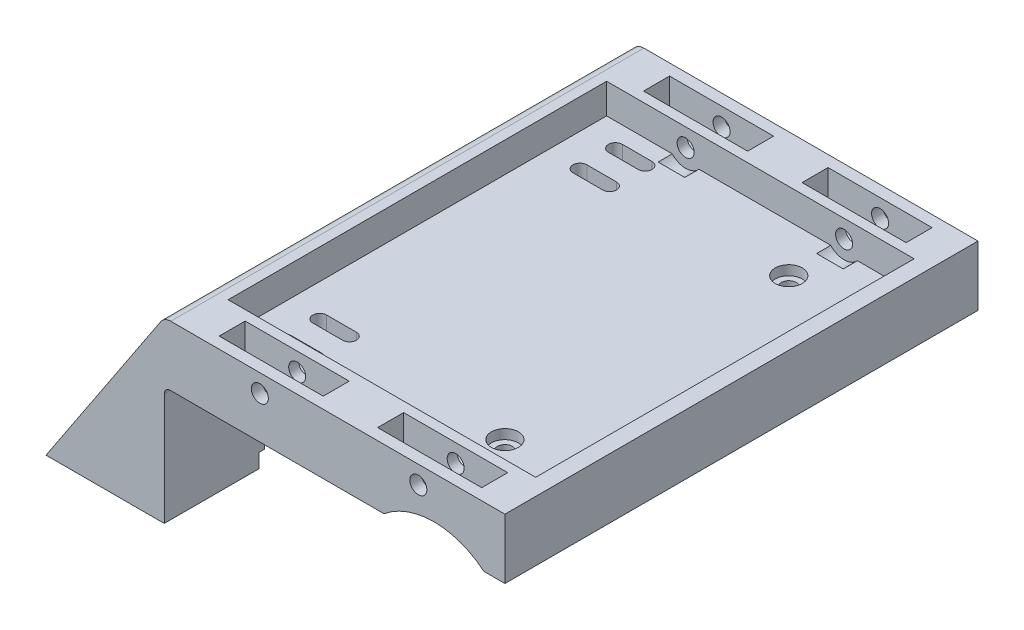
SolidWorks part; units mm, degrees
ref_plane "Front Plane" through (0, 0, 0) normal (0, 0, 1) x (1, 0, 0)
ref_plane "Top Plane" through (0, 0, 0) normal (0, 1, 0) x (1, 0, 0)
ref_plane "Right Plane" through (0, 0, 0) normal (1, 0, 0) x (0, 0, -1)
sketch "Sketch1" plane through (0, 0, 0) normal (0, 1, 0) x (1, 0, 0)
  line L1 (-35.4822, 73.1783) -> (36.5178, 73.1783)
  line L2 (-35.4822, 73.1783) -> (-35.4822, -26.8217)
  line L3 (-35.4822, -26.8217) -> (36.5178, -26.8217)
  line L4 (36.5178, 73.1783) -> (36.5178, -26.8217)
  dimension "D1" = 72
  dimension "D2" = 100
extrude "Boss-Extrude1" add sketch "Sketch1" against normal blind 12.7
sketch "Sketch2" plane through (0, 0, 0) normal (0, 1, 0) x (1, 0, 0)
  line L0 (-35.4822, -26.8217) -> (36.5178, -26.8217) construction
  line L1 (-31.9822, 63.1783) -> (33.0178, 63.1783)
  line L2 (-31.9822, 63.1783) -> (-31.9822, -16.8217)
  line L3 (-31.9822, -16.8217) -> (33.0178, -16.8217)
  line L4 (33.0178, 63.1783) -> (33.0178, -16.8217)
  line L7 (36.5178, 73.1783) -> (-35.4822, 73.1783) construction
  line L8 (0.5178, 63.1783) -> (0.5178, -16.8217) construction
  line L9 (0.5178, 73.1783) -> (0.5178, -26.8217) construction
  dimension "D1" = 10
  dimension "D2" = 65
  dimension "D4" = 10
extrude "Cut-Extrude1" cut sketch "Sketch2" against normal blind 6.35
sketch "Sketch4" plane through (0, 0, 26.8217) normal (0, 0, 1) x (1, 0, 0)
  line L0 (-35.4822, -12.7) -> (-35.4822, -37.7)
  line L1 (-35.4822, -37.7) -> (-60.4822, -37.7)
  line L2 (-60.4822, -37.7) -> (-35.4822, 0)
  line L3 (-35.4822, 0) -> (-35.4822, -12.7)
  dimension "D1" = 25
  dimension "D2" = 25
extrude "Boss-Extrude2" add sketch "Sketch4" against normal up to surface (100 mm away) up to face at (0.5178, -6.35, -73.1783)
fillet "Fillet1" radius 2.54 1 edges at (-35.4822, 0, -23.1783)
sketch "Sketch5" plane through (0, 0, -73.1783) normal (0, 0, -1) x (-1, 0, 0)
  line L3 (-36.5178, -12.7) -> (-36.5178, 0) construction
  line L4 (-36.5178, -12.7) -> (35.4822, -12.7) construction
  circle A0 centre (-21.5178, -25.4) radius 16.51
  dimension "D1" = 33.02
  dimension "D2" = 15
  dimension "D3" = 12.7
extrude "Cut-Extrude2" cut sketch "Sketch5" against normal blind 16
sketch "Sketch7" plane through (0, -6.35, 0) normal (0, 1, 0) x (1, 0, 0)
  line L0 (-25.1272, 58.1783) -> (-18.8372, 58.1783) construction
  line L1 (-25.1272, 59.6431) -> (-18.8372, 59.6431)
  line L2 (-25.1272, 56.7135) -> (-18.8372, 56.7135)
  line L3 (-31.9822, 23.1783) -> (33.0178, 23.1783) construction
  line L4 (-31.9822, 63.1783) -> (-31.9822, -16.8217) construction
  line L5 (33.0178, -16.8217) -> (33.0178, 63.1783) construction
  line L6 (36.5178, 73.1783) -> (-34.1188, 73.1783) construction
  line L8 (-25.1272, 50.6783) -> (-18.8372, 50.6783) construction
  line L9 (-25.1272, 52.1431) -> (-18.8372, 52.1431)
  line L10 (-25.1272, 49.2135) -> (-18.8372, 49.2135)
  line L11 (-25.1272, -11.8217) -> (-18.8372, -11.8217) construction
  line L12 (-25.1272, -13.2865) -> (-18.8372, -13.2865)
  line L13 (-25.1272, -10.3569) -> (-18.8372, -10.3569)
  line L14 (-25.1272, -4.3217) -> (-18.8372, -4.3217) construction
  line L16 (-31.9822, 63.1783) -> (-31.9822, -16.8217) construction
  line L17 (-25.1272, -5.7865) -> (-18.8372, -5.7865)
  line L18 (-25.1272, -2.8569) -> (-18.8372, -2.8569)
  arc A0 (-25.1272, 59.6431) -> (-25.1272, 56.7135) centre (-25.1272, 58.1783) ccw
  arc A1 (-18.8372, 56.7135) -> (-18.8372, 59.6431) centre (-18.8372, 58.1783) ccw
  arc A2 (-25.1272, -13.2865) -> (-25.1272, -10.3569) centre (-25.1272, -11.8217) cw
  arc A3 (-18.8372, -10.3569) -> (-18.8372, -13.2865) centre (-18.8372, -11.8217) cw
  arc A4 (-25.1272, 52.1431) -> (-25.1272, 49.2135) centre (-25.1272, 50.6783) ccw
  arc A5 (-18.8372, 49.2135) -> (-18.8372, 52.1431) centre (-18.8372, 50.6783) ccw
  arc A6 (-25.1272, -5.7865) -> (-25.1272, -2.8569) centre (-25.1272, -4.3217) cw
  arc A7 (-18.8372, -2.8569) -> (-18.8372, -5.7865) centre (-18.8372, -4.3217) cw
  point P2 (-21.9822, 58.1783)
  point P17 (-21.9822, -11.8217)
  point P20 (-21.9822, 50.6783)
  point P31 (-21.9822, -4.3217)
  dimension "D1" = 15
  dimension "D3" = 7.5
  dimension "D4" = 10
extrude "Cut-Extrude3" cut sketch "Sketch7" against normal up to surface (6.35 mm away) up to face at (9.6991, -12.7, -50.4283)
sketch "Sketch9" plane through (0, -6.35, 0) normal (0, 1, 0) x (1, 0, 0)
  line L0 (33.0178, 23.1783) -> (-31.9822, 23.1783) construction
  line L1 (33.0178, -16.8217) -> (33.0178, 63.1783) construction
  line L2 (-31.9822, 63.1783) -> (-31.9822, -16.8217) construction
  line L3 (16.5178, 53.1783) -> (16.5178, -6.8217) construction
  line L4 (36.5178, -26.8217) -> (36.5178, 73.1783) construction
  point P9 (16.5178, 23.1783)
  point P10 (16.5178, 53.1783)
  point P11 (16.5178, -6.8217)
  dimension "D1" = 30
  dimension "D2" = 20
hole_wizard "CBORE for M2 Pan Head Machine Screw1" positions "Sketch11" profile "Sketch10" counterbore size "M2" standard "ANSI Metric" end condition through all
sketch "Sketch11" plane through (0, -6.35, 0) normal (0, 1, 0) x (1, 0, 0)
  point P0 (16.5178, 53.1783)
  point P3 (16.5178, -6.8217)
sketch "Sketch10" plane through (16.5178, -6.35, -53.1783) normal (1, 0, 0) x (0, 0, 1)
  line L0 (0, 0) -> (0, 31.35)
  line L1 (0, 31.35) -> (1.5875, 31.35)
  line L3 (1.5875, 31.35) -> (1.5875, 2.032)
  line L4 (1.5875, 2.032) -> (2.8575, 2.032)
  line L5 (2.8575, 2.032) -> (2.8575, 0)
  line L7 (2.8575, 0) -> (0, 0)
  line L11 (0, -6.35) -> (0, 107.95) construction
  dimension "Thru Hole Dia." = 3.175
  dimension "Thru Hole Depth" = 31.35
  dimension "C'Bore Dia." = 5.715
  dimension "C'Bore Depth" = 2.032
sketch "Sketch13" plane through (0, -37.7, 0) normal (0, -1, 0) x (1, 0, 0)
  line L0 (-35.4822, -73.1783) -> (-35.4822, 26.8217) construction
  line L1 (-35.4822, -10.4783) -> (-51.3072, -10.4783)
  line L2 (-35.4822, -10.4783) -> (-35.4822, -35.8783)
  line L3 (-35.4822, -35.8783) -> (-51.3072, -35.8783)
  line L4 (-54.4822, -13.6533) -> (-54.4822, -32.7033)
  line L7 (-35.4822, -23.1783) -> (-54.4822, -23.1783) construction
  line L8 (33.0178, -23.1783) -> (-31.9822, -23.1783) construction
  line L9 (-51.3072, -10.4783) -> (-54.4822, -13.6533)
  line L10 (-51.3072, -35.8783) -> (-54.4822, -32.7033)
  dimension "D1" = 3.175
  dimension "D2" = 3.175
  dimension "D3" = 25.4
  dimension "D4" = 19
extrude "Cut-Extrude4" cut sketch "Sketch13" against normal blind 11
ref_plane "Plane1" through (0, 0, -23.1783) normal (0, 0, 1) x (1, 0, 0)
mirror "Mirror1" about plane through (0, 0, -23.1783) normal (0, 0, 1) of "Cut-Extrude2"
sketch "Sketch14" plane through (0, -26.7, 0) normal (0, -1, 0) x (1, 0, 0)
  line L0 (-35.4822, -23.1783) -> (-51.5551, -23.1783) construction
  line L1 (-35.4822, -35.8783) -> (-35.4822, -10.4783) construction
  line L3 (-43.5187, -23.1783) -> (-43.5187, -15.8123) construction
  line L4 (-43.5187, -23.1783) -> (-43.5187, -30.5443) construction
  point P10 (-43.5187, -15.8123)
  point P11 (-43.5187, -30.5443)
  dimension "D1" = 14.732
hole_wizard "9/64 (0.14063) Diameter Hole1" positions "Sketch17" profile "Sketch15" hole size "9/64" standard "ANSI Inch" end condition through all
sketch "Sketch17" plane through (0, -26.7, 0) normal (0, -1, 0) x (-1, 0, 0)
  point P0 (43.5187, 15.8123)
  point P3 (43.5187, 30.5443)
sketch "Sketch15" plane through (-43.5187, -26.7, -15.8123) normal (1, 0, 0) x (0, 0, -1)
  line L0 (0, 0) -> (0, 26.7)
  line L1 (0, 26.7) -> (1.786, 26.7)
  line L2 (1.786, 26.7) -> (1.786, 0)
  line L5 (1.786, 0) -> (0, 0)
  line L11 (0, -6.35) -> (0, 107.95) construction
  dimension "Thru Hole Dia." = 3.572
  dimension "Thru Hole Depth" = 26.7
sketch "Sketch18" plane through (0, -26.7, 0) normal (0, -1, 0) x (1, 0, 0)
  line L1 (-43.5187, -27.6114) -> (-46.0587, -29.0778)
  line L2 (-46.0587, -29.0778) -> (-46.0587, -32.0108)
  line L3 (-46.0587, -32.0108) -> (-43.5187, -33.4772)
  line L4 (-43.5187, -33.4772) -> (-40.9787, -32.0108)
  line L5 (-40.9787, -32.0108) -> (-40.9787, -29.0778)
  line L6 (-40.9787, -29.0778) -> (-43.5187, -27.6114)
  line L7 (-43.5187, -18.7452) -> (-40.9787, -17.2788)
  line L8 (-40.9787, -17.2788) -> (-40.9787, -14.3458)
  line L9 (-40.9787, -14.3458) -> (-43.5187, -12.8794)
  line L10 (-43.5187, -12.8794) -> (-46.0587, -14.3458)
  line L11 (-46.0587, -14.3458) -> (-46.0587, -17.2788)
  line L12 (-46.0587, -17.2788) -> (-43.5187, -18.7452)
  circle A0 centre (-43.5187, -30.5443) radius 2.54 construction
  circle A1 centre (-43.5187, -15.8123) radius 2.54 construction
  dimension "D1" = 5.08
  dimension "D2" = 5.08
extrude "Cut-Extrude5" cut sketch "Sketch18" along direction (0, 1, 0) on the side against the normal through all from offset 4.445 offset against normal yes
sketch "Sketch19" plane through (0, -37.7, 0) normal (0, -1, 0) x (1, 0, 0)
  line L0 (-35.4822, -73.1783) -> (-35.4822, 26.8217) construction
  line L1 (-35.4822, -1.1783) -> (-51.4822, -1.1783)
  line L2 (-35.4822, -1.1783) -> (-35.4822, 6.8217)
  line L3 (-35.4822, 6.8217) -> (-51.4822, 6.8217)
  line L4 (-51.4822, -1.1783) -> (-51.4822, 6.8217)
  line L5 (-51.4822, 2.8217) -> (-35.4822, 2.8217) construction
  line L6 (-60.4822, 26.8217) -> (-35.4822, 26.8217) construction
  line L7 (-60.4822, -23.1783) -> (-35.4822, -23.1783) construction
  line L8 (-60.4822, -73.1783) -> (-60.4822, 26.8217) construction
  line L9 (-35.4822, -23.1783) -> (-51.5551, -23.1783) construction
  line L16 (-51.4822, -49.1783) -> (-35.4822, -49.1783) construction
  line L17 (-35.4822, -53.1783) -> (-51.4822, -53.1783)
  line L18 (-35.4822, -45.1783) -> (-51.4822, -45.1783)
  line L23 (-51.4822, -45.1783) -> (-51.4822, -53.1783)
  line L25 (-35.4822, -45.1783) -> (-35.4822, -53.1783)
  point P8 (-39.9822, 2.8217)
  point P23 (-39.9822, -49.1783)
  dimension "D1" = 8
  dimension "D2" = 16
  dimension "D3" = 4.5
  dimension "D4" = 20
extrude "Cut-Extrude6" cut sketch "Sketch19" against normal blind 3
sketch "Sketch22" plane through (0, -37.7, 0) normal (0, -1, 0) x (-1, 0, 0)
  line L0 (35.4822, 49.1783) -> (51.4822, 49.1783) construction
  line L1 (35.4822, 53.1783) -> (35.4822, 45.1783) construction
  line L2 (51.4822, 45.1783) -> (51.4822, 53.1783) construction
  point P6 (47.4822, 49.1783)
  dimension "D1" = 4
hole_wizard "M2 Clearance Hole1" positions "Sketch24" profile "Sketch23" hole size "M2" standard "ANSI Metric"
sketch "Sketch24" plane through (0, -34.7, 0) normal (0, -1, 0) x (-1, 0, 0)
  point P0 (47.4822, 49.1783)
sketch "Sketch23" plane through (-47.4822, -34.7, -49.1783) normal (1, 0, 0) x (0, 0, -1)
  line L0 (0, 0) -> (0, 10.721)
  line L1 (0, 10.721) -> (1.2, 10)
  line L2 (1.2, 10) -> (1.2, 0)
  line L5 (1.2, 0) -> (0, 0)
  line L10 (0, 10.721) -> (-1.2, 10) construction
  line L11 (0, -6.35) -> (0, 107.95) construction
  dimension "Hole Dia." = 2.4
  dimension "Hole Depth" = 10
  dimension "Drill Angle" = 118
mirror "Mirror2" about plane through (0, 0, -23.1783) normal (0, 0, 1) of "M2 Clearance Hole1"
sketch "Sketch25" plane through (-35.4822, 0, 0) normal (1, 0, 0) x (0, 0, -1)
  line L0 (-5.6217, -31.7) -> (-5.6217, -34.7)
  line L1 (-5.6217, -26.7) -> (-0.0217, -26.7)
  line L2 (-5.6217, -26.7) -> (-5.6217, -31.7)
  line L4 (-0.0217, -26.7) -> (-0.0217, -31.7)
  line L5 (-6.8217, -37.7) -> (-6.8217, -34.7) construction
  line L6 (1.1783, -37.7) -> (1.1783, -34.7) construction
  line L7 (1.1783, -34.7) -> (1.1783, -37.7) construction
  line L8 (1.1783, -34.7) -> (1.1783, -37.7) construction
  line L10 (-2.8217, -37.7) -> (-2.8217, -26.7) construction
  line L11 (-6.8217, -37.7) -> (1.1783, -37.7) construction
  line L12 (1.1783, -34.7) -> (-6.8217, -34.7) construction
  line L13 (-5.6217, -34.7) -> (-0.0217, -34.7)
  line L14 (-6.8217, -34.7) -> (1.1783, -34.7) construction
  line L15 (-0.0217, -34.7) -> (-0.0217, -31.7)
  point P21 (-2.8217, -26.7)
  dimension "D1" = 8
  dimension "D2" = 5
  dimension "D3" = 5.6
extrude "Cut-Extrude8" cut sketch "Sketch25" against normal blind 4
mirror "Mirror4" about plane through (0, 0, -23.1783) normal (0, 0, 1) of "Cut-Extrude8"
fillet "Fillet2" radius 1.27 1 edges
fillet "Fillet3" radius 0.762 4 edges at (-54.4822, -33.176, -13.6533) (-51.3072, -32.2, -10.4783) (-51.3072, -32.2, -35.8783) (-54.4822, -33.176, -32.7033)
sketch "Sketch29" plane through (0, 0, 0) normal (0, 1, 0) x (1, 0, 0)
  line L0 (36.5178, -26.8217) -> (36.5178, 73.1783) construction
  line L1 (36.5178, 73.1783) -> (-34.1188, 73.1783) construction
  line L4 (-31.9822, 23.1783) -> (33.0178, 23.1783) construction
  circle A1 centre (-23.4822, 68.1783) radius 2.25
  circle A2 centre (26.5178, 68.1783) radius 2.25
  circle A3 centre (26.5178, -21.8217) radius 2.25
  circle A4 centre (-23.4822, -21.8217) radius 2.25
  dimension "D1" = 4.5
  dimension "D2" = 50
  dimension "D5" = 10
  dimension "D3" = 5
  dimension "D4" = 5
extrude "Cut-Extrude9" [suppressed] cut sketch "Sketch29" against normal blind 5 draft 1
sketch "Sketch30" plane through (0, 0, 0) normal (0, 1, 0) x (1, 0, 0)
  line L0 (-31.9822, 23.1783) -> (33.0178, 23.1783) construction
  line L1 (-26.2822, 70.7783) -> (-4.2822, 70.7783)
  line L2 (-26.2822, 70.7783) -> (-26.2822, 65.2783)
  line L3 (-26.2822, 65.2783) -> (-4.2822, 65.2783)
  line L4 (-4.2822, 70.7783) -> (-4.2822, 65.2783)
  line L5 (7.2178, 70.7783) -> (29.2178, 70.7783)
  line L6 (7.2178, 70.7783) -> (7.2178, 65.2783)
  line L7 (7.2178, 65.2783) -> (29.2178, 65.2783)
  line L8 (29.2178, 70.7783) -> (29.2178, 65.2783)
  line L9 (29.2178, -24.4217) -> (29.2178, -18.9217)
  line L10 (7.2178, -18.9217) -> (29.2178, -18.9217)
  line L11 (7.2178, -24.4217) -> (7.2178, -18.9217)
  line L12 (7.2178, -24.4217) -> (29.2178, -24.4217)
  line L13 (-4.2822, -24.4217) -> (-4.2822, -18.9217)
  line L14 (-26.2822, -18.9217) -> (-4.2822, -18.9217)
  line L15 (-26.2822, -24.4217) -> (-26.2822, -18.9217)
  line L16 (-26.2822, -24.4217) -> (-4.2822, -24.4217)
  line L17 (36.5178, -26.8217) -> (36.5178, 73.1783) construction
  dimension "D1" = 11.5
  dimension "D2" = 22
  dimension "D3" = 22
  dimension "D4" = 5.5
  dimension "D5" = 7.3
  dimension "D6" = 42.1
extrude "Cut-Extrude10" cut sketch "Sketch30" against normal blind 7.5
sketch "Sketch31" plane through (0, 0, 26.8217) normal (0, 0, 1) x (1, 0, 0)
  line L0 (-34.1188, 0) -> (36.5178, 0) construction
  line L1 (36.5178, -12.7) -> (36.5178, 0) construction
  circle A0 centre (-15.2822, -3.8) radius 1.8
  circle A1 centre (18.2178, -3.8) radius 1.8
  dimension "D2" = 3.6
  dimension "D1" = 3.8
  dimension "D3" = 18.3
  dimension "D4" = 33.5
extrude "Cut-Extrude11" cut sketch "Sketch31" against normal up to surface (100 mm away) up to face at (-9.5532, -14.8832, -73.1783)
sketch "Sketch32" plane through (0, 0, -63.1783) normal (0, 0, 1) x (1, 0, 0)
  circle A0 centre (-15.2822, -3.8) radius 3.8
  circle A1 centre (18.2178, -3.8) radius 3.8
extrude "Cut-Extrude12" cut sketch "Sketch32" along normal blind 3
